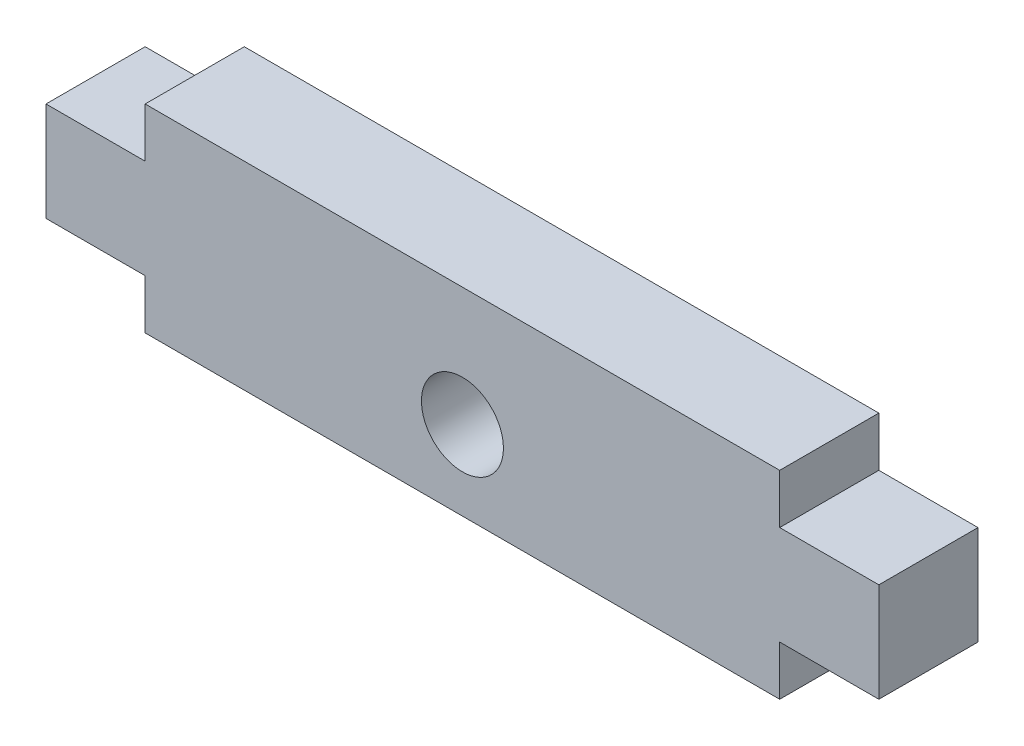
SolidWorks part; units mm, degrees
ref_plane "Front Plane" through (0, 0, 0) normal (0, 0, 1) x (1, 0, 0)
ref_plane "Top Plane" through (0, 0, 0) normal (0, 1, 0) x (1, 0, 0)
ref_plane "Right Plane" through (0, 0, 0) normal (1, 0, 0) x (0, 0, -1)
sketch "Sketch1" plane through (0, 0, 0) normal (0, 0, 1) x (1, 0, 0)
  line L0 (0, 2.5) -> (0, 7.5)
  line L1 (0, -55) -> (0, 55) construction
  line L2 (0, 7.5) -> (5, 7.5)
  line L3 (5, 10) -> (5, 7.5)
  line L4 (55, 0) -> (-55, 0) construction
  line L5 (5, 0) -> (37, 0)
  line L6 (37, 7.5) -> (37, 10)
  line L7 (37, 7.5) -> (42, 7.5)
  line L8 (42, 7.5) -> (42, 2.5)
  line L9 (42, 2.5) -> (37, 2.5)
  line L10 (37, 2.5) -> (37, 0)
  line L11 (37, 10) -> (5, 10)
  line L12 (5, 2.5) -> (5, 0)
  line L13 (5, 2.5) -> (0, 2.5)
  dimension "D1" = 32
  dimension "D2" = 5
  dimension "D3" = 10
  dimension "D4" = 5
extrude "Boss-Extrude1" add sketch "Sketch1" along normal blind 5
sketch "Sketch2" plane through (0, 0, 5) normal (0, 0, 1) x (1, 0, 0)
  line L0 (2.75, 0) -> (-2.75, 0) construction
  circle A0 centre (21, 4) radius 2.0675
  dimension "D1" = 4.135
  dimension "D2" = 4
extrude "Cut-Extrude1" cut sketch "Sketch2" against normal through all
